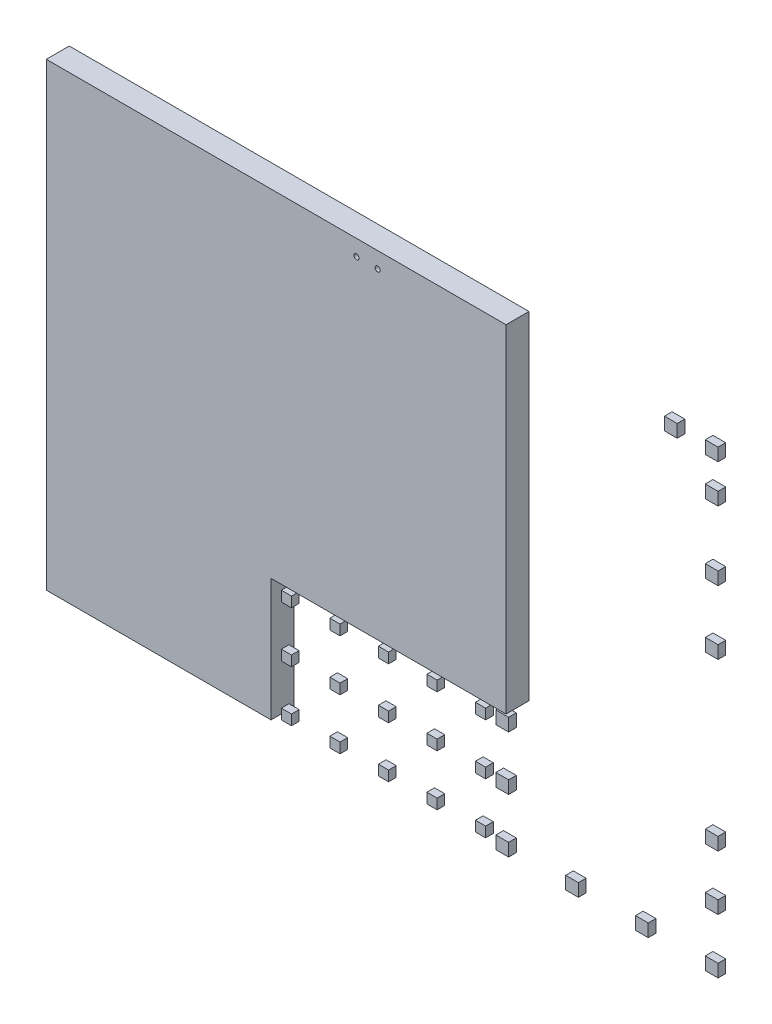
SolidWorks part; units mm, degrees
ref_plane "Спереди" through (0, 0, 0) normal (0, 0, 1) x (1, 0, 0)
ref_plane "Сверху" through (0, 0, 0) normal (0, 1, 0) x (1, 0, 0)
ref_plane "Справа" through (0, 0, 0) normal (1, 0, 0) x (0, 0, -1)
sketch "Эскиз1" plane through (0, 0, 0) normal (0, 0, 1) x (1, 0, 0)
  line L0 (0, 0) -> (9000, 0)
  line L1 (9000, 0) -> (9000, -6600)
  line L2 (9000, -6600) -> (4400, -6600)
  line L3 (4400, -6600) -> (4400, -9000)
  line L4 (4400, -9000) -> (0, -9000)
  line L5 (0, -9000) -> (0, 0)
  line L6 (8800, -6600) -> (8800, -9000) construction
  line L7 (8800, -9000) -> (9050, -9000)
  line L8 (8800, -9000) -> (8800, -8750)
  line L9 (8800, -8750) -> (9050, -8750)
  line L14 (9050, -9000) -> (9050, -8750)
  line L15 (9000, -203) -> (9000, -2700) construction
  line L16 (8797, -6600) -> (4400, -6600) construction
  line L17 (4400, -8797) -> (4400, -6603) construction
  line L18 (203, -9000) -> (4200, -9000) construction
  line L19 (8800, -6630) -> (9050, -6630)
  line L20 (8800, -6630) -> (8800, -6880)
  line L21 (8800, -6880) -> (9050, -6880)
  line L22 (9050, -6630) -> (9050, -6880)
  line L23 (9050, -6880) -> (9050, -7690) construction
  line L24 (8800, -7690) -> (9050, -7690)
  line L25 (8800, -7690) -> (8800, -7940)
  line L26 (8800, -7940) -> (9050, -7940)
  line L27 (9050, -7690) -> (9050, -7940)
  line L28 (9050, -7940) -> (9050, -8750) construction
  line L29 (13150, -9000) -> (0, -9000) construction
  line L30 (10166.6667, -8750) -> (10416.6667, -8750)
  line L31 (10166.6667, -8750) -> (10166.6667, -9000)
  line L32 (10166.6667, -9000) -> (10416.6667, -9000)
  line L33 (10416.6667, -8750) -> (10416.6667, -9000)
  line L34 (9050, -8750) -> (10166.6667, -8750) construction
  line L35 (11533.3333, -8750) -> (11783.3333, -8750)
  line L36 (11533.3333, -8750) -> (11533.3333, -9000)
  line L37 (11533.3333, -9000) -> (11783.3333, -9000)
  line L38 (11783.3333, -8750) -> (11783.3333, -9000)
  line L43 (12900, -8750) -> (13150, -8750)
  line L44 (12900, -8750) -> (12900, -9000)
  line L45 (12900, -9000) -> (13150, -9000)
  line L46 (13150, -8750) -> (13150, -9000)
  line L47 (10416.6667, -8750) -> (11533.3333, -8750) construction
  line L48 (11783.3333, -8750) -> (12900, -8750) construction
  line L49 (13150, -4500) -> (13150, -9000) construction
  line L50 (13150, -6600) -> (12900, -6600)
  line L51 (13150, -6600) -> (13150, -6850)
  line L52 (13150, -6850) -> (12900, -6850)
  line L53 (12900, -6600) -> (12900, -6850)
  line L54 (13150, -7675) -> (12900, -7675)
  line L55 (13150, -7675) -> (13150, -7925)
  line L56 (13150, -7925) -> (12900, -7925)
  line L57 (12900, -7675) -> (12900, -7925)
  line L58 (12900, -7675) -> (12900, -6850) construction
  line L59 (13150, -3600) -> (12900, -3600)
  line L60 (13150, -3600) -> (13150, -3350)
  line L61 (13150, -3350) -> (12900, -3350)
  line L62 (12900, -3600) -> (12900, -3350)
  line L63 (13150, -2100) -> (12900, -2100)
  line L64 (13150, -2100) -> (13150, -2350)
  line L65 (13150, -2350) -> (12900, -2350)
  line L66 (12900, -2100) -> (12900, -2350)
  line L67 (13150, -1000) -> (12900, -1000)
  line L68 (13150, -1000) -> (13150, -750)
  line L69 (13150, -750) -> (12900, -750)
  line L70 (12900, -1000) -> (12900, -750)
  line L71 (13150, 0) -> (12900, 0)
  line L72 (13150, 0) -> (13150, -250)
  line L73 (13150, -250) -> (12900, -250)
  line L74 (12900, 0) -> (12900, -250)
  line L75 (12100, 0) -> (12350, 0)
  line L76 (12100, 0) -> (12100, -250)
  line L77 (12100, -250) -> (12350, -250)
  line L78 (12350, 0) -> (12350, -250)
  line L79 (12900, -7925) -> (12900, -8750) construction
  line L80 (4800, -6900) -> (4800, -7700) construction
  line L81 (4600, -6700) -> (4800, -6700)
  line L82 (4600, -6700) -> (4600, -6900)
  line L83 (4600, -6900) -> (4800, -6900)
  line L84 (4800, -6700) -> (4800, -6900)
  line L85 (4600, -7700) -> (4800, -7700)
  line L86 (4600, -7700) -> (4600, -7900)
  line L87 (4600, -7900) -> (4800, -7900)
  line L88 (4800, -7700) -> (4800, -7900)
  line L89 (4600, -8700) -> (4800, -8700)
  line L90 (4600, -8700) -> (4600, -8900)
  line L91 (4600, -8900) -> (4800, -8900)
  line L92 (4800, -8700) -> (4800, -8900)
  line L93 (4800, -7900) -> (4800, -8700) construction
  line L94 (5550, -6700) -> (5550, -6900)
  line L95 (5550, -6700) -> (5750, -6700)
  line L96 (5750, -6700) -> (5750, -6900)
  line L97 (5550, -6900) -> (5750, -6900)
  line L98 (5550, -7700) -> (5550, -7900)
  line L99 (5550, -7700) -> (5750, -7700)
  line L100 (5750, -7700) -> (5750, -7900)
  line L101 (5550, -7900) -> (5750, -7900)
  line L102 (5550, -8700) -> (5550, -8900)
  line L103 (5550, -8700) -> (5750, -8700)
  line L104 (5750, -8700) -> (5750, -8900)
  line L105 (5550, -8900) -> (5750, -8900)
  line L106 (6500, -6700) -> (6500, -6900)
  line L107 (6500, -6700) -> (6700, -6700)
  line L108 (6700, -6700) -> (6700, -6900)
  line L109 (6500, -6900) -> (6700, -6900)
  line L110 (6500, -7700) -> (6500, -7900)
  line L111 (6500, -7700) -> (6700, -7700)
  line L112 (6700, -7700) -> (6700, -7900)
  line L113 (6500, -7900) -> (6700, -7900)
  line L114 (6500, -8700) -> (6500, -8900)
  line L115 (6500, -8700) -> (6700, -8700)
  line L116 (6700, -8700) -> (6700, -8900)
  line L117 (6500, -8900) -> (6700, -8900)
  line L118 (7450, -6700) -> (7450, -6900)
  line L119 (7450, -6700) -> (7650, -6700)
  line L120 (7650, -6700) -> (7650, -6900)
  line L121 (7450, -6900) -> (7650, -6900)
  line L122 (7450, -7700) -> (7450, -7900)
  line L123 (7450, -7700) -> (7650, -7700)
  line L124 (7650, -7700) -> (7650, -7900)
  line L125 (7450, -7900) -> (7650, -7900)
  line L126 (7450, -8700) -> (7450, -8900)
  line L127 (7450, -8700) -> (7650, -8700)
  line L128 (7650, -8700) -> (7650, -8900)
  line L129 (7450, -8900) -> (7650, -8900)
  line L130 (8400, -6700) -> (8400, -6900)
  line L131 (8400, -6700) -> (8600, -6700)
  line L132 (8600, -6700) -> (8600, -6900)
  line L133 (8400, -6900) -> (8600, -6900)
  line L134 (8400, -7700) -> (8400, -7900)
  line L135 (8400, -7700) -> (8600, -7700)
  line L136 (8600, -7700) -> (8600, -7900)
  line L137 (8400, -7900) -> (8600, -7900)
  line L138 (8400, -8700) -> (8400, -8900)
  line L139 (8400, -8700) -> (8600, -8700)
  line L140 (8600, -8700) -> (8600, -8900)
  line L141 (8400, -8900) -> (8600, -8900)
  circle A0 centre (6486.2448, -312.4922) radius 50
  circle A1 centre (6070.9439, -312.4922) radius 50
  dimension "D3" = 100
  dimension "D1" = 250
  dimension "D2" = 30
  dimension "D4" = 810
  dimension "D5" = 1116.6667
  dimension "D6" = 200
  dimension "D7" = 100
  dimension "D8" = 100
  dimension "D9" = 200
  dimension "D11" = 950
  dimension "D10" = 5
extrude "Бобышка-Вытянуть1" add sketch "Эскиз1" against normal blind 150
sketch "Эскиз2" plane through (0, 0, -150) normal (0, 0, -1) x (-1, 0, 0)
  line L0 (-450, -8550) -> (-450, -450)
  line L1 (-450, -450) -> (-8550, -450)
  line L2 (-8550, -450) -> (-8550, -6150)
  line L3 (-8550, -6150) -> (-3950, -6150)
  line L4 (-3950, -6150) -> (-3950, -8550)
  line L5 (-3950, -8550) -> (-450, -8550)
  line L6 (0, -9000) -> (0, 0)
  line L7 (0, 0) -> (-9000, 0)
  line L8 (-9000, 0) -> (-9000, -6600)
  line L9 (-9000, -6600) -> (-4400, -6600)
  line L10 (-4400, -6600) -> (-4400, -9000)
  line L11 (-4400, -9000) -> (0, -9000)
  line L12 (0, -9000) -> (0, 0)
  line L13 (0, 0) -> (-9000, 0)
  line L14 (-9000, 0) -> (-9000, -6600)
  line L15 (-9000, -6600) -> (-4400, -6600)
  line L16 (-4400, -6600) -> (-4400, -9000)
  line L17 (-4400, -9000) -> (0, -9000)
  dimension "D1" = 0
  dimension "D2" = 450
extrude "Бобышка-Вытянуть2" add sketch "Эскиз2" along normal blind 300
